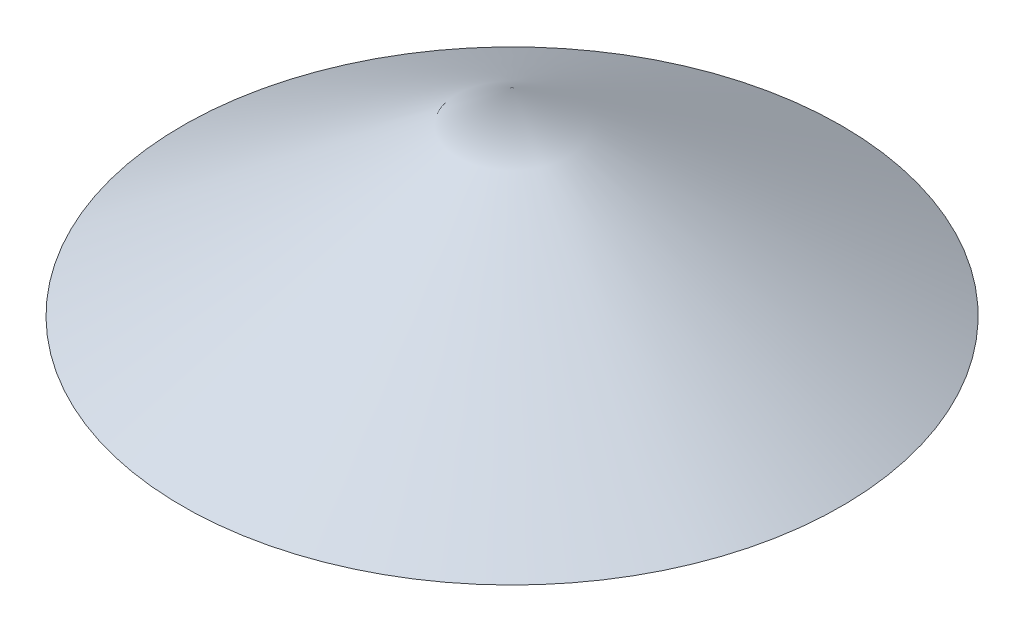
SolidWorks part; units mm, degrees
ref_plane "Front Plane" through (0, 0, 0) normal (0, 0, 1) x (1, 0, 0)
ref_plane "Top Plane" through (0, 0, 0) normal (0, 1, 0) x (1, 0, 0)
ref_plane "Right Plane" through (0, 0, 0) normal (1, 0, 0) x (0, 0, -1)
sketch "Sketch1" plane through (0, 0, 0) normal (0, 0, 1) x (1, 0, 0)
  line L0 (0, 0) -> (0, 38.1)
  line L1 (0, 38.1) -> (63.5, 0)
  line L2 (63.5, 0) -> (0, 0)
  dimension "D1" = 38.1
  dimension "D2" = 63.5
revolve "Revolve1" add sketch "Sketch1" angle 360 about L0
